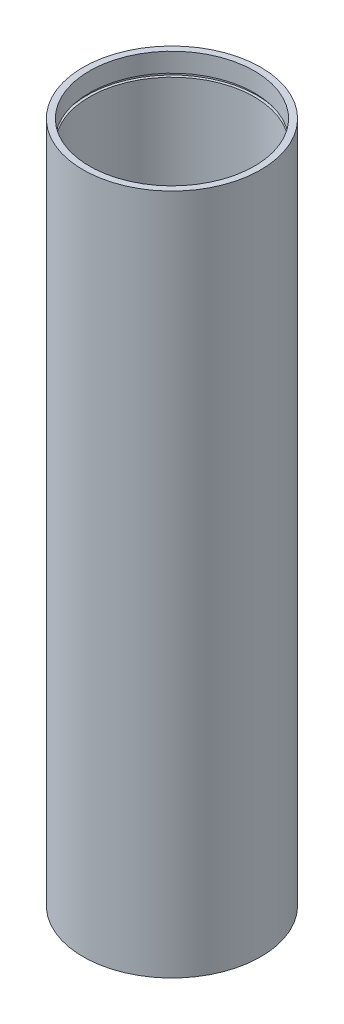
SolidWorks part; units mm, degrees
material "1060 Alloy"
ref_plane "Front Plane" through (0, 0, 0) normal (0, 0, 1) x (1, 0, 0)
ref_plane "Top Plane" through (0, 0, 0) normal (0, 1, 0) x (1, 0, 0)
ref_plane "Right Plane" through (0, 0, 0) normal (1, 0, 0) x (0, 0, -1)
sketch "Sketch2" plane through (0, 0, 0) normal (0, 0, 1) x (1, 0, 0)
  line L0 (0, 0) -> (0, 365.76) construction
  line L1 (41.275, 11.2522) -> (42.5958, 11.2522)
  line L2 (42.5958, 11.2522) -> (42.5958, 9.525)
  line L3 (41.275, 0) -> (44.45, 0)
  line L4 (41.275, 340.9442) -> (41.275, 331.4192)
  line L5 (41.275, 340.9442) -> (44.45, 340.9442)
  line L6 (44.45, 0) -> (44.45, 340.9442)
  line L7 (42.5958, 9.525) -> (41.275, 9.525)
  line L8 (41.275, 329.692) -> (42.5958, 329.692)
  line L9 (42.5958, 329.692) -> (42.5958, 331.4192)
  line L10 (42.5958, 331.4192) -> (41.275, 331.4192)
  line L11 (41.275, 329.692) -> (41.275, 11.2522)
  line L12 (41.275, 11.2522) -> (41.2565, 11.2265)
  line L13 (41.275, 9.525) -> (41.275, 0)
  line L14 (0, -55) -> (0, 55) construction
  dimension "D2" = 9.525
  dimension "D3" = 3.175
  dimension "D4" = 340.9442
  dimension "D5" = 9.525
  dimension "D6" = 1.7272
  dimension "D7" = 1.3208
  dimension "D9" = 1.3208
  dimension "D10" = 1.7272
revolve "Revolve1" add sketch "Sketch2" angle 360 about L0 region at (42.8664, 170.4721, 0)
